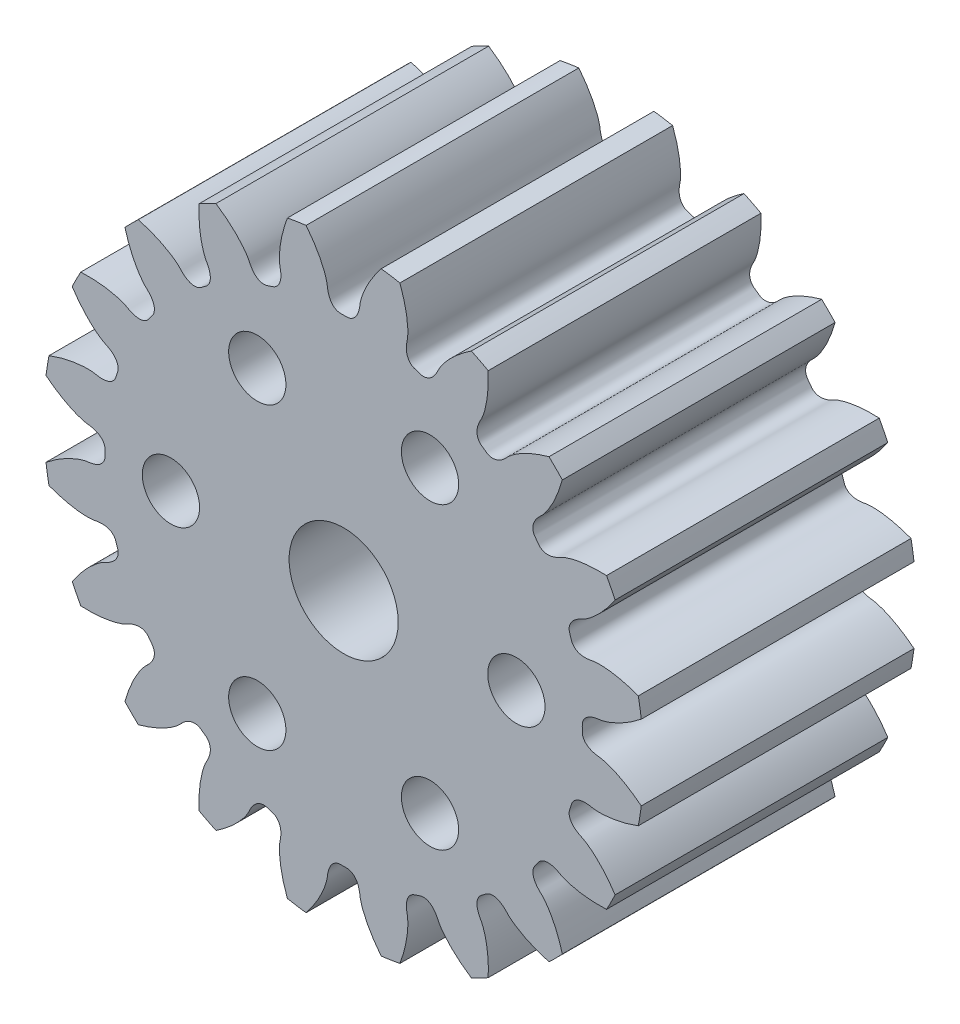
SolidWorks part; units mm, degrees
ref_plane "Front Plane" through (0, 0, 0) normal (0, 0, 1) x (1, 0, 0)
ref_plane "Top Plane" through (0, 0, 0) normal (0, 1, 0) x (1, 0, 0)
ref_plane "Right Plane" through (0, 0, 0) normal (1, 0, 0) x (0, 0, -1)
ref_axis "Axis1" through (0, 0, 55) along (0, 0, -1)
sketch "SketchRevolveSpurPinion" plane through (0, 0, 0) normal (1, 0, 0) x (0, 0, -1)
  line L0 (0, 0) -> (1, 0) construction
  line L1 (-7.5, 0) -> (-7.5, 16.5)
  line L2 (-7.5, 16.5) -> (7.5, 16.5)
  line L3 (7.5, 16.5) -> (7.5, 0)
  line L4 (7.5, 0) -> (-7.5, 0)
  dimension "Side1" = 7.5
  dimension "OutsideRadius" = 16.5
  dimension "Side2" = 7.5
revolve "SpurPinion" add sketch "SketchRevolveSpurPinion" angle 360 about L0
sketch "SketchToothSpurPinion" plane through (0, 0, 0) normal (0, 0, 1) x (1, 0, 0)
  arc A0 (16.4388, 2.1204) -> (16.4388, -2.1204) centre (0, 0) cw
  spline S0 degree 3 poles (16.4388, -2.1204) (16.3062, -2.0126) (16.1079, -1.8609) (15.8417, -1.6767) (15.6549, -1.5557) (15.4759, -1.4476) (15.3054, -1.3516) (15.1441, -1.2672) (14.9923, -1.1937) (14.8506, -1.1305) (14.7196, -1.0767) (14.5996, -1.0318) (14.491, -0.9949) (14.3942, -0.9653) (14.3096, -0.9423) (14.2375, -0.925) (14.178, -0.9127) (14.0868, -0.8965) (14.0005, -0.8895) (13.9171, -0.8753) (13.8763, -0.8676) (13.8362, -0.859) (13.797, -0.8497) (13.7585, -0.8395) (13.7207, -0.8284) (13.6837, -0.8165) (13.6473, -0.8036) (13.6116, -0.7897) (13.5765, -0.7747) (13.542, -0.7586) (13.508, -0.7412) (13.4746, -0.7225) (13.4416, -0.7022) (13.4091, -0.6802) (13.3771, -0.6563) (13.3457, -0.6302) (13.3149, -0.6017) (13.285, -0.5705) (13.256, -0.5362) (13.2285, -0.4988) (13.2028, -0.4578) (13.1796, -0.4131) (13.1594, -0.365) (13.1431, -0.3135) (13.1313, -0.2592) (13.1253, -0.2069) (13.1227, -0.1203) (13.1268, 0) (13.1227, 0.1203) (13.1253, 0.2069) (13.1313, 0.2592) (13.1431, 0.3135) (13.1594, 0.365) (13.1796, 0.4131) (13.2028, 0.4578) (13.2285, 0.4988) (13.256, 0.5362) (13.285, 0.5705) (13.3149, 0.6017) (13.3457, 0.6302) (13.3771, 0.6563) (13.4091, 0.6802) (13.4416, 0.7022) (13.4746, 0.7225) (13.508, 0.7412) (13.542, 0.7586) (13.5765, 0.7747) (13.6116, 0.7897) (13.6473, 0.8036) (13.6837, 0.8165) (13.7207, 0.8284) (13.7585, 0.8395) (13.797, 0.8497) (13.8362, 0.859) (13.8763, 0.8676) (13.9171, 0.8753) (14.0005, 0.8895) (14.0868, 0.8965) (14.178, 0.9127) (14.2375, 0.925) (14.3096, 0.9423) (14.3942, 0.9653) (14.491, 0.9949) (14.5996, 1.0318) (14.7196, 1.0767) (14.8506, 1.1305) (14.9923, 1.1937) (15.1441, 1.2672) (15.3054, 1.3516) (15.4759, 1.4476) (15.6549, 1.5557) (15.8417, 1.6767) (16.1079, 1.8609) (16.3062, 2.0126) (16.4388, 2.1204) knots 0 0 0 0 0.061397 0.089672 0.116331 0.141374 0.164802 0.186614 0.20681 0.225391 0.242356 0.257705 0.271439 0.283556 0.294059 0.302945 0.310216 0.315871 0.336221 0.341283 0.346262 0.351165 0.355996 0.360762 0.36547 0.370128 0.374744 0.37933 0.383895 0.388453 0.393018 0.397607 0.402236 0.406928 0.411702 0.416584 0.421597 0.426769 0.432124 0.437685 0.443471 0.449491 0.455745 0.462217 0.468878 0.475679 0.481075 0.5 0.518925 0.524321 0.531122 0.537783 0.544255 0.550509 0.556529 0.562315 0.567876 0.573231 0.578403 0.583416 0.588298 0.593072 0.597764 0.602393 0.606982 0.611547 0.616105 0.62067 0.625256 0.629872 0.63453 0.639238 0.644004 0.648835 0.653738 0.658717 0.663779 0.684129 0.689784 0.697055 0.705941 0.716444 0.728561 0.742295 0.757644 0.774609 0.79319 0.813386 0.835198 0.858626 0.883669 0.910328 0.938603 1 1 1 1
extrude "ToothExtrudeCutSpurPinion" cut sketch "SketchToothSpurPinion" against normal blind 7.5 and the other way blind 7.5
pattern_circular "PatternSpurPinion" count 20 every 18 about axis through (0, 0, 55) along (0, 0, -1) of "ToothExtrudeCutSpurPinion"
sketch "BoreRevolveSketch" plane through (0, 0, 0) normal (1, 0, 0) x (0, 0, -1)
  line L0 (0, 0) -> (1, 0) construction
  line L1 (-7.5, 0) -> (7.5, 0)
  line L2 (7.5, 0) -> (7.5, 6.35)
  line L3 (7.5, 6.35) -> (-7.5, 6.35)
  line L4 (-7.5, 6.35) -> (-7.5, 0)
  dimension "BoreSide1" = 7.5
  dimension "TaperSide1" = 6.35
  dimension "BoreSide2" = 7.5
  dimension "TaperSide2" = 6.35
revolve "BoreRevolveCut" cut sketch "BoreRevolveSketch" angle 360 about L0
sketch "AuxiliarySketchSpurPinion" plane through (0, 0, 0) normal (0, 0, 1) x (1, 0, 0)
  circle A0 centre (0, 0) radius 15 construction
  circle A1 centre (0, 0) radius 14.0954 construction
  circle A2 centre (0, 0) radius 14.1048 construction
  circle A3 centre (0, 0) radius 16.5 construction
  circle A4 centre (0, 0) radius 13.125 construction
  dimension "PitchDiameter" = 30
  dimension "BaseDiameter" = 28.1908
  dimension "FormDiameter" = 28.2095
  dimension "MajorDiameter" = 33
  dimension "MinorDiameter" = 26.25
sketch "Sketch6" plane through (0, 0, 7.5) normal (0, 0, 1) x (1, 0, 0)
  circle A0 centre (0, 0) radius 6.35
extrude "Boss-Extrude1" add sketch "Sketch6" against normal blind 15
sketch "Sketch7" plane through (0, 0, 7.5) normal (0, 0, 1) x (1, 0, 0)
  line L0 (0, 0) -> (-9.5, 0) construction
  line L1 (0, 0) -> (-4.4095, 7.6375) construction
  line L2 (0, 0) -> (-4.75, 8.2272) construction
  line L3 (0, 0) -> (4.75, 8.2272) construction
  line L4 (0, 0) -> (9.5, 0) construction
  line L5 (0, 0) -> (4.75, -8.2272) construction
  line L6 (0, 0) -> (-4.75, -8.2272) construction
  circle A0 centre (-9.5, 0) radius 1.575
  circle A1 centre (-4.75, 8.2272) radius 1.575
  circle A2 centre (4.75, 8.2272) radius 1.575
  circle A3 centre (9.5, 0) radius 1.575
  circle A4 centre (4.75, -8.2272) radius 1.575
  circle A5 centre (-4.75, -8.2272) radius 1.575
  point P18 (0, 0)
  dimension "D2" = 3.15
  dimension "D1" = 9.5
  dimension "D3" = 60
  dimension "D4" = 6
extrude "Cut-Extrude2" cut sketch "Sketch7" against normal blind 15
sketch "Sketch10" plane through (0, 0, 7.5) normal (0, 0, 1) x (1, 0, 0)
  circle A0 centre (0, 0) radius 3
  dimension "D1" = 6
extrude "Cut-Extrude3" cut sketch "Sketch10" against normal through all
